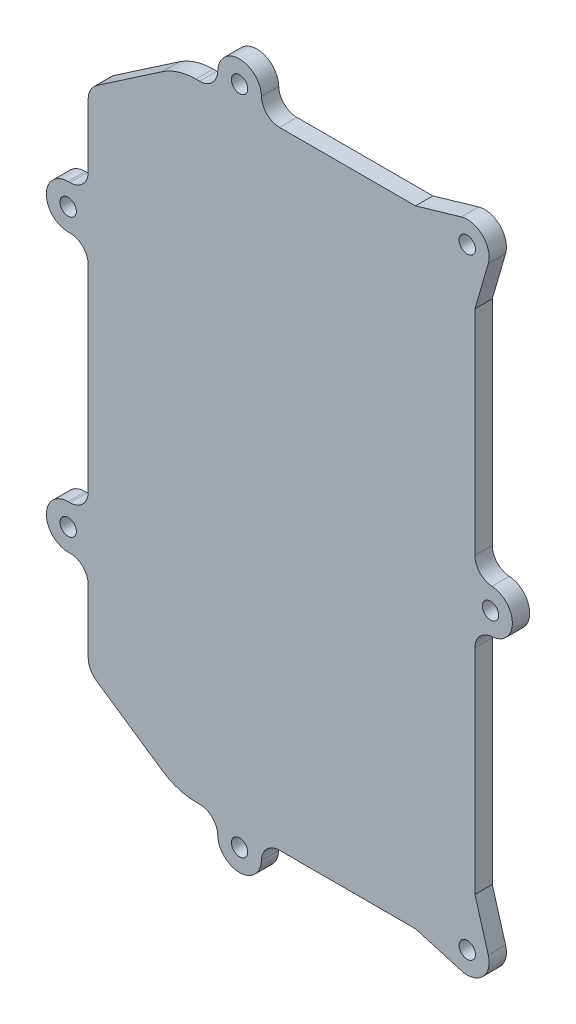
SolidWorks part; units mm, degrees
material "Acrylic (Medium-high impact)"
ref_plane "X-Y Datum" through (0, 0, 0) normal (0, 0, 1) x (1, 0, 0)
ref_plane "X-Z Datum" through (0, 0, 0) normal (0, 1, 0) x (1, 0, 0)
ref_plane "Y-Z Datum" through (0, 0, 0) normal (1, 0, 0) x (0, 0, -1)
sketch "Sketch1" plane through (0, 0, 0) normal (0, 0, 1) x (1, 0, 0)
  line L113 (-97.8326, 37.4754) -> (-97.8326, 20.1138)
  line L114 (-103.3326, 42.4754) -> (-102.8326, 42.4754)
  line L115 (-102.8326, 54.4754) -> (-103.3326, 54.4754)
  line L116 (-97.8326, 113.6412) -> (-97.8326, 59.4754)
  line L117 (-103.3326, 118.6412) -> (-102.8326, 118.6412)
  line L118 (-102.8326, 130.6412) -> (-103.3326, 130.6412)
  line L119 (-97.8326, 153.0028) -> (-97.8326, 135.6412)
  line L120 (-77.4488, 169.7199) -> (-95.5034, 157.4099)
  line L121 (-67.2451, 172.5583) -> (-68.2472, 172.5583)
  line L122 (-7.9166, 172.5583) -> (-45.2494, 172.5583)
  line L123 (4.6315, 176.21) -> (-7.9166, 172.5583)
  line L124 (8.4174, 156.2243) -> (12.0691, 168.7725)
  line L125 (8.4174, 97.5349) -> (8.4174, 156.2243)
  line L126 (8.4174, 16.8923) -> (8.4174, 75.5817)
  line L127 (12.0691, 4.3442) -> (8.4174, 16.8923)
  line L128 (-7.9166, 0.5583) -> (4.6315, -3.0933)
  line L129 (-45.2494, 0.5583) -> (-7.9166, 0.5583)
  line L130 (-68.2472, 0.5583) -> (-67.2451, 0.5583)
  line L131 (-95.5034, 15.7067) -> (-77.4488, 3.3967)
  arc A101 (-97.8326, 37.4754) -> (-102.8326, 42.4754) centre (-102.8326, 37.4754) ccw
  arc A102 (-103.3326, 54.4754) -> (-103.3326, 42.4754) centre (-103.3326, 48.4754) ccw
  arc A103 (-102.8326, 54.4754) -> (-97.8326, 59.4754) centre (-102.8326, 59.4754) ccw
  arc A104 (-97.8326, 113.6412) -> (-102.8326, 118.6412) centre (-102.8326, 113.6412) ccw
  arc A105 (-103.3326, 130.6412) -> (-103.3326, 118.6412) centre (-103.3326, 124.6412) ccw
  arc A106 (-102.8326, 130.6412) -> (-97.8326, 135.6412) centre (-102.8326, 135.6412) ccw
  arc A107 (-95.5034, 157.4099) -> (-97.8326, 153.0028) centre (-92.4986, 153.0028) ccw
  arc A108 (-68.2472, 172.5583) -> (-77.4488, 169.7199) centre (-68.2472, 156.2243) ccw
  arc A109 (-67.2451, 172.5583) -> (-62.2461, 177.4596) centre (-67.2451, 177.5583) ccw
  arc A110 (-50.2484, 177.4596) -> (-62.2461, 177.4596) centre (-56.2472, 177.341) ccw
  arc A111 (-50.2484, 177.4596) -> (-45.2494, 172.5583) centre (-45.2494, 177.5583) ccw
  arc A112 (12.0691, 168.7725) -> (4.6315, 176.21) centre (6.3081, 170.449) ccw
  arc A113 (8.4174, 97.5349) -> (13.0914, 92.5456) centre (13.4174, 97.5349) ccw
  arc A114 (13.0914, 80.5711) -> (13.0914, 92.5456) centre (12.7001, 86.5583) ccw
  arc A115 (13.0914, 80.5711) -> (8.4174, 75.5817) centre (13.4174, 75.5817) ccw
  arc A116 (4.6315, -3.0933) -> (12.0691, 4.3442) centre (6.3081, 2.6677) ccw
  arc A117 (-45.2494, 0.5583) -> (-50.2484, -4.3429) centre (-45.2494, -4.4417) ccw
  arc A118 (-62.2461, -4.3429) -> (-50.2484, -4.3429) centre (-56.2472, -4.2244) ccw
  arc A119 (-62.2461, -4.3429) -> (-67.2451, 0.5583) centre (-67.2451, -4.4417) ccw
  arc A120 (-77.4488, 3.3967) -> (-68.2472, 0.5583) centre (-68.2472, 16.8923) ccw
  arc A121 (-97.8326, 20.1138) -> (-95.5034, 15.7067) centre (-92.4986, 20.1138) ccw
extrude "Boss-Extrude1" add sketch "Sketch1" against normal blind 4.7625
hole_wizard "M4 Clearance Hole1" positions "Sketch4" profile "Sketch3" hole size "M4" standard "ANSI Metric" end condition through all
sketch "Sketch4" plane through (0, 0, -4.7625) normal (0, 0, -1) x (-1, 0, 0)
  point P0 (103.3326, 48.4754)
  point P2 (56.2472, -4.2244)
  point P6 (-12.7001, 86.5583)
  point P10 (56.2472, 177.341)
  point P12 (103.3326, 124.6412)
  point P15 (-6.3081, 2.6677)
  point P20 (-6.3081, 170.449)
sketch "Sketch3" plane through (-103.3326, 48.4754, -4.7625) normal (1, 0, 0) x (0, 1, 0)
  line L0 (0, 0) -> (0, 4.7625)
  line L1 (0, 4.7625) -> (2.25, 4.7625)
  line L2 (2.25, 4.7625) -> (2.25, 0)
  line L5 (2.25, 0) -> (0, 0)
  line L11 (0, -6.35) -> (0, 107.95) construction
  dimension "Thru Hole Dia." = 4.5
  dimension "Thru Hole Depth" = 4.7625
